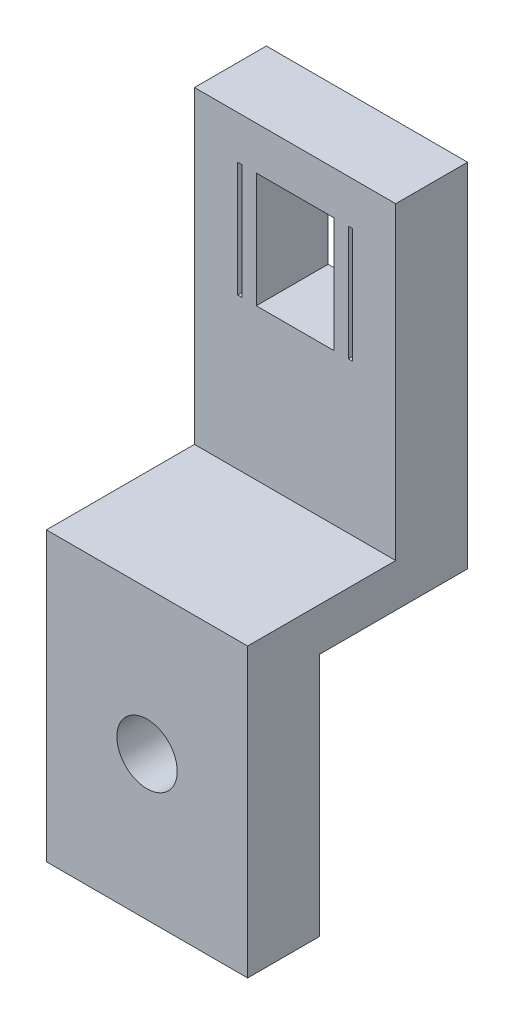
SolidWorks part; units mm, degrees
ref_plane "Front Plane" through (0, 0, 0) normal (0, 0, 1) x (1, 0, 0)
ref_plane "Top Plane" through (0, 0, 0) normal (0, 1, 0) x (1, 0, 0)
ref_plane "Right Plane" through (0, 0, 0) normal (1, 0, 0) x (0, 0, -1)
sketch "Sketch1" plane through (0, 0, 0) normal (0, 0, 1) x (1, 0, 0)
  line L0 (4.3, 38.5) -> (4.3, 30.5)
  line L1 (0, 0) -> (14, 0)
  line L2 (0, 0) -> (0, 41.5)
  line L3 (0, 41.5) -> (14, 41.5)
  line L4 (14, 0) -> (14, 41.5)
  line L9 (3, 38.5) -> (11, 38.5)
  line L10 (3, 38.5) -> (3, 30.5)
  line L11 (3, 30.5) -> (11, 30.5)
  line L12 (11, 38.5) -> (11, 30.5)
  line L13 (3.3, 38.5) -> (10.7, 38.5)
  line L14 (3.3, 38.5) -> (3.3, 30.5)
  line L15 (3.3, 30.5) -> (10.7, 30.5)
  line L16 (10.7, 38.5) -> (10.7, 30.5)
  line L17 (9.7, 38.5) -> (9.7, 30.5)
  circle A1 centre (7, 10) radius 2.1
  dimension "D7" = 4.2
  dimension "D8" = 10
  dimension "D1" = 14
  dimension "D2" = 41.5
  dimension "D3" = 8
  dimension "D4" = 8
  dimension "D5" = 38.5
  dimension "D6" = 3
  dimension "D10" = 7
  dimension "D12" = 0.3
  dimension "D13" = 0.3
  dimension "D14" = 1
  dimension "D15" = 1
extrude "Boss-Extrude3" add sketch "Sketch1" along normal blind 15.3 contours L1 L4 L3 L2 A1 L9 L13 L12 L11 L15 L10 | L9 L14 L11 L0 | L13 L17 L15 L16 region at (3.8, 34.5, 0) region at (10.2, 34.5, 0) region at (7, 19.297, 0)
sketch "Sketch2" plane through (0, 0, 0) normal (-1, 0, 0) x (0, 0, 1)
  line L0 (15.3, 0) -> (15.3, 41.5) construction
  line L1 (0, 0) -> (10.3, 0)
  line L2 (0, 0) -> (0, 17)
  line L3 (0, 17) -> (10.3, 17)
  line L4 (10.3, 0) -> (10.3, 17)
  line L5 (15.3, 41.5) -> (5, 41.5)
  line L6 (15.3, 41.5) -> (15.3, 20)
  line L7 (15.3, 20) -> (5, 20)
  line L8 (5, 41.5) -> (5, 20)
  line L9 (0, 0) -> (0, 41.5) construction
  dimension "D1" = 5
  dimension "D2" = 5
  dimension "D3" = 17
  dimension "D4" = 3
extrude "Cut-Extrude1" cut sketch "Sketch2" against normal blind 21
